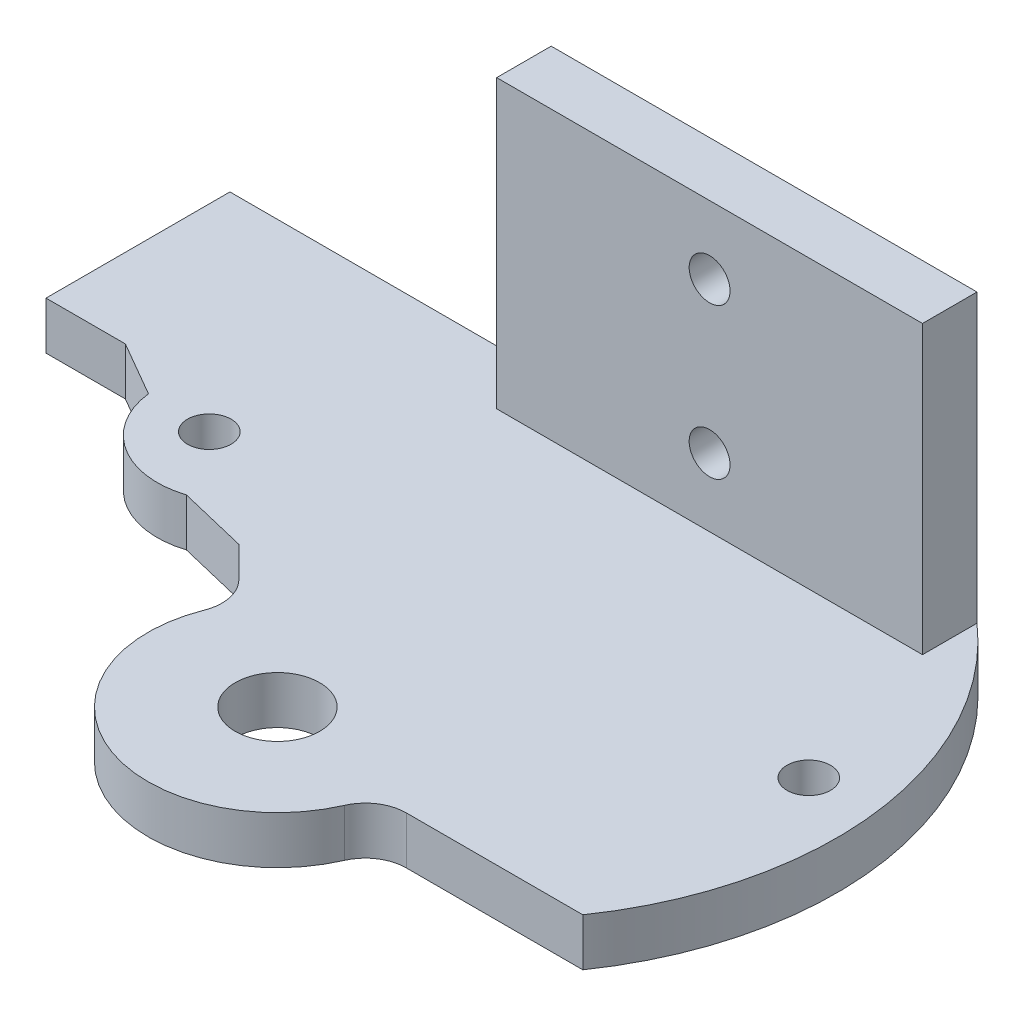
SolidWorks part; units mm, degrees
ref_plane "Alzado" through (0, 0, 0) normal (0, 0, 1) x (1, 0, 0)
ref_plane "Planta" through (0, 0, 0) normal (0, 1, 0) x (1, 0, 0)
ref_plane "Vista lateral" through (0, 0, 0) normal (1, 0, 0) x (0, 0, -1)
sketch "Croquis1" plane through (0, 0, 0) normal (0, 1, 0) x (1, 0, 0)
  line L0 (-35, 32.5) -> (35, -32.5) construction
  line L1 (-35, 32.5) -> (35, 32.5)
  line L2 (-35, 32.5) -> (-35, -32.5)
  line L3 (-35, -32.5) -> (35, -32.5)
  line L4 (35, 32.5) -> (35, -32.5)
  dimension "D1" = 70
  dimension "D2" = 65
extrude "Extruir1" add sketch "Croquis1" along normal blind 3.5
sketch "Croquis2" plane through (0, 3.5, 0) normal (0, 1, 0) x (1, 0, 0)
  line L0 (0, 32.5) -> (0, -32.5) construction
  line L1 (35, 32.5) -> (-35, 32.5) construction
  line L2 (-35, -32.5) -> (35, -32.5) construction
  circle A0 centre (0, -17.5) radius 3.1
  dimension "D1" = 6.2
  dimension "D2" = 15
extrude "Extruir2" cut sketch "Croquis2" against normal blind 5
sketch "Croquis3" plane through (0, 3.5, 0) normal (0, 1, 0) x (1, 0, 0)
  line L0 (0, -32.5) -> (0, 32.5) construction
  line L1 (-35, -32.5) -> (35, -32.5) construction
  line L2 (35, 32.5) -> (-35, 32.5) construction
  line L3 (-32.9868, -32.5) -> (-32.9868, 32.5) construction
  line L4 (-32.9868, 1.5) -> (-12.9615, 1.5)
  line L5 (18.8496, -32.5) -> (18.8496, 32.5) construction
  line L6 (-32.9868, 3.5) -> (18.8496, 3.5) construction
  line L7 (-32.9868, 2) -> (0, 2) construction
  line L8 (-32.9868, 11.5) -> (18.8496, 11.5) construction
  line L9 (0, -17.5) -> (-14.8492, -2.6508) construction
  line L10 (0, -17.5) -> (14.8492, -2.6508) construction
  line L11 (0, 2) -> (18.8496, 2) construction
  line L12 (-32.9868, 2) -> (18.8496, 2) construction
  line L13 (-32.9868, 12) -> (18.8496, 12)
  line L14 (-5.3033, -12.1967) -> (-16.2635, -1.2365) construction
  line L15 (12.9615, 1.5) -> (18.8496, 1.5)
  line L16 (-32.9868, 1.5) -> (18.8496, 1.5) construction
  line L17 (7.9844, -18) -> (22.9946, -18)
  line L18 (-5.9993, -12.2078) -> (-16.6132, -1.5939)
  line L19 (0, -17.5) -> (23, -17.5) construction
  line L20 (7.5, -17.5) -> (23, -17.5) construction
  line L21 (-5.6569, -12.5503) -> (-16.617, -1.5901) construction
  line L22 (7.5, -18) -> (23, -18) construction
  line L23 (-32.9868, 12) -> (-32.9868, 1.5)
  line L24 (18.8496, 12) -> (18.8496, 1.5)
  line L25 (-34.4868, 13.5) -> (20.3496, 13.5)
  line L26 (20.3496, 13.5) -> (20.3496, 0)
  line L27 (17.1464, 0) -> (20.3496, 0)
  line L28 (9.2871, -19.5) -> (24.4182, -19.5)
  line L29 (-7.9812, -12.3473) -> (-18.6805, -1.6479)
  line L30 (-34.4868, 0) -> (-17.1464, 0)
  line L31 (-34.4868, 13.5) -> (-34.4868, 0)
  circle A0 centre (0, -17.5) radius 21 construction
  circle A1 centre (0, -17.5) radius 7.5 construction
  arc A2 (-12.9615, 1.5) -> (-16.6132, -1.5939) centre (0, -17.5) ccw
  circle A3 centre (0, -17.5) radius 23 construction
  arc A4 (-5.9993, -12.2078) -> (7.9844, -18) centre (0, -17.5) ccw
  arc A5 (22.9946, -18) -> (12.9615, 1.5) centre (0, -17.5) ccw
  arc A6 (24.4182, -19.5) -> (17.1464, 0) centre (0, -17.5) ccw
  arc A7 (-7.9812, -12.3473) -> (9.2871, -19.5) centre (0, -17.5) ccw
  arc A8 (-17.1464, 0) -> (-18.6805, -1.6479) centre (0, -17.5) ccw
  dimension "D3" = 42
  dimension "D8" = 15
  dimension "D9" = 46
  dimension "D14" = 0.5
  dimension "D2" = 51.8364
  dimension "D6" = 90
  dimension "D7" = 45
  dimension "D1" = 32.9868
  dimension "D4" = 1.5
  dimension "D5" = 9.5
  dimension "D10" = 2
  dimension "D11" = 0.5
  dimension "D12" = 0.5
  dimension "D13" = 0.5
  dimension "D15" = 1.5
extrude "Extruir3" add sketch "Croquis3" along normal blind 10
sketch "Croquis4" plane through (0, 3.5, 0) normal (0, 1, 0) x (1, 0, 0)
  line L0 (-34.4868, 0) -> (-17.1464, 0) construction
  line L1 (-34.4868, 13.5) -> (-34.4868, 0) construction
  line L2 (20.3496, 13.5) -> (-34.4868, 13.5) construction
  line L3 (20.3496, 0) -> (20.3496, 13.5) construction
  line L4 (17.1464, 0) -> (20.3496, 0) construction
  line L5 (9.2871, -19.5) -> (24.4182, -19.5) construction
  line L6 (-18.6805, -1.6479) -> (-7.9812, -12.3473) construction
  line L7 (-34.4868, 0) -> (-17.1464, 0)
  line L8 (-34.4868, 13.5) -> (-34.4868, 0)
  line L9 (20.3496, 13.5) -> (-34.4868, 13.5)
  line L10 (20.3496, 0) -> (20.3496, 13.5)
  line L11 (17.1464, 0) -> (20.3496, 0)
  line L12 (9.2871, -19.5) -> (24.4182, -19.5)
  line L13 (-18.6805, -1.6479) -> (-7.9812, -12.3473)
  arc A0 (-17.1464, 0) -> (-18.6805, -1.6479) centre (0, -17.5) ccw construction
  arc A1 (24.4182, -19.5) -> (17.1464, 0) centre (0, -17.5) ccw construction
  arc A2 (-7.9812, -12.3473) -> (9.2871, -19.5) centre (0, -17.5) ccw construction
  arc A3 (-17.1464, 0) -> (-18.6805, -1.6479) centre (0, -17.5) ccw
  arc A4 (24.4182, -19.5) -> (17.1464, 0) centre (0, -17.5) ccw
  arc A5 (-7.9812, -12.3473) -> (9.2871, -19.5) centre (0, -17.5) ccw
extrude "Extruir4" cut sketch "Croquis4" against normal blind 10 flip side to cut
fillet "Redondeo1" radius 3 4 edges at (9.2871, 6.75, 19.5) (-7.9812, 6.75, 12.3473) (7.9844, 8.5, 18) (-5.9993, 8.5, 12.2078)
sketch "Croquis5" plane through (0, 0, 0) normal (0, -1, 0) x (1, 0, 0)
  line L0 (-18.6805, 1.6479) -> (-9.5151, 10.8133) construction
  line L1 (-34.4868, 0) -> (-17.1464, 0) construction
  line L2 (-18.6805, 1.6479) -> (-14.4379, 5.8906)
  line L3 (-24.4498, 0) -> (-17.1464, 0)
  line L4 (20.3496, 0) -> (20.3496, -13.5) construction
  line L5 (17.1464, 0) -> (20.3496, 0) construction
  line L6 (20.3496, 0) -> (20.3496, -13.5)
  line L7 (17.1464, 0) -> (20.3496, 0)
  arc A0 (-14.4379, 5.8906) -> (-24.4498, 0) centre (-18.6805, 1.6479) ccw
  arc A1 (-18.6805, 1.6479) -> (-17.1464, 0) centre (0, 17.5) ccw construction
  arc A2 (-18.6805, 1.6479) -> (-17.1464, 0) centre (0, 17.5) ccw
  arc A3 (24.4182, 19.5) -> (20.3496, -13.5) centre (3.8531, 5.2847) cw
  arc A4 (17.1464, 0) -> (24.4182, 19.5) centre (0, 17.5) ccw construction
  arc A5 (17.1464, 0) -> (24.4182, 19.5) centre (0, 17.5) ccw
  dimension "D1" = 12
  dimension "D2" = 25
extrude "Extruir5" add sketch "Croquis5" against normal up to surface (13.5 mm away) up to face at (-1.8278, 13.5, 5.5887)
chamfer "Chaflán1" distance 5 angle 45 2 edges at (-14.4379, 6.75, 5.8906) (-24.4498, 6.75, 0) first distance on face at (-20.5835, 6.75, 4.8823) first distance on face at (-29.4683, 6.75, 0)
sketch "Croquis6" plane through (0, 13.5, 0) normal (0, 1, 0) x (1, 0, 0)
  line L7 (-34.4868, 13.5) -> (-34.4868, 0)
  line L8 (-34.4868, 0) -> (-28.6614, 0)
  line L9 (-28.6614, 0) -> (-24.6424, -2.3231)
  line L10 (-16.83, -7.3554) -> (-11.7523, -8.5761)
  line L11 (-11.7523, -8.5761) -> (-9.5151, -10.8133)
  line L12 (11.4564, -19.5) -> (24.4182, -19.5)
  line L13 (20.3496, 13.5) -> (-34.4868, 13.5)
  line L14 (-34.4868, 13.5) -> (-34.4868, 0)
  line L15 (-34.4868, 0) -> (-28.6614, 0)
  line L16 (-28.6614, 0) -> (-24.6424, -2.3231)
  line L17 (-16.83, -7.3554) -> (-11.7523, -8.5761)
  line L18 (-11.7523, -8.5761) -> (-9.5151, -10.8133)
  line L19 (11.4564, -19.5) -> (24.4182, -19.5)
  line L20 (20.3496, 13.5) -> (-34.4868, 13.5)
  arc A5 (-24.6424, -2.3231) -> (-16.83, -7.3554) centre (-18.6805, -1.6479) ccw
  arc A6 (-8.8437, -14.0303) -> (-9.5151, -10.8133) centre (-11.6365, -12.9346) ccw
  arc A7 (-8.8437, -14.0303) -> (8.7069, -21.3) centre (0, -17.5) ccw
  arc A8 (11.4564, -19.5) -> (8.7069, -21.3) centre (11.4564, -22.5) ccw
  arc A9 (24.4182, -19.5) -> (20.3496, 13.5) centre (3.8531, -5.2847) ccw
  arc A10 (-24.6424, -2.3231) -> (-16.83, -7.3554) centre (-18.6805, -1.6479) ccw
  arc A11 (-8.8437, -14.0303) -> (-9.5151, -10.8133) centre (-11.6365, -12.9346) ccw
  arc A12 (-8.8437, -14.0303) -> (8.7069, -21.3) centre (0, -17.5) ccw
  arc A13 (11.4564, -19.5) -> (8.7069, -21.3) centre (11.4564, -22.5) ccw
  arc A14 (24.4182, -19.5) -> (20.3496, 13.5) centre (3.8531, -5.2847) ccw
  dimension "D1" = 0
extrude "Extruir6" add sketch "Croquis6" along normal blind 3.5 separate body
sketch "Croquis7" plane through (0, 17, 0) normal (0, 1, 0) x (1, 0, 0)
  line L0 (20.3496, 13.5) -> (-34.4868, 13.5) construction
  circle A0 centre (-20, -2.5) radius 1.6
  circle A1 centre (24, -2.5) radius 1.6
  dimension "D1" = 3.2
  dimension "D2" = 16
  dimension "D3" = 20
  dimension "D4" = 24
extrude "Extruir7" cut sketch "Croquis7" against normal through all
sketch "Croquis8" plane through (0, 17, 0) normal (0, 1, 0) x (1, 0, 0)
  circle A0 centre (0, -17.5) radius 3.1 construction
  circle A1 centre (0, -17.5) radius 3.1
extrude "Extruir8" cut sketch "Croquis8" against normal blind 5
sketch "Croquis9" plane through (0, 13.5, 0) normal (0, 1, 0) x (1, 0, 0)
  line L0 (18.8496, 1.5) -> (18.8496, 12) construction
  line L1 (18.8496, 1.5) -> (18.8496, 12)
  line L2 (19.5496, 1.5) -> (19.5496, 12)
  line L3 (18.8496, 12) -> (19.5496, 12)
  line L4 (18.8496, 1.5) -> (19.5496, 1.5)
  dimension "D1" = 0.7
extrude "Extruir9" cut sketch "Croquis9" against normal up to surface (10 mm away) up to face at (-1.6185, 3.5, 4.8365)
sketch "Croquis10" plane through (19.5496, 0, 0) normal (-1, 0, 0) x (0, 0, 1)
  line L0 (-5.875, 13.5) -> (-5.875, 3.5) construction
  line L3 (-1.5, 13.5) -> (-12, 13.5) construction
  line L4 (-12, 3.5) -> (-12, 13.5) construction
  line L5 (-5.875, 13.5) -> (-12, 3.5) construction
  line L6 (-12, 3.5) -> (-1.5, 3.5) construction
  line L7 (-8.9375, 8.5) -> (-12, 13.5) construction
  line L8 (19.5, 13.5) -> (-13.5, 13.5) construction
  line L10 (-7.4062, 11) -> (-10.4687, 11)
  line L11 (-7.4062, 11) -> (-7.4062, 6)
  line L12 (-7.4062, 6) -> (-10.4687, 6)
  line L13 (-10.4687, 11) -> (-10.4687, 6)
  dimension "D1" = 6.125
  dimension "D2" = 5
  dimension "D3" = 3.0625
extrude "Extruir10" cut sketch "Croquis10" against normal blind 10 and the other way through all
delete or keep bodies "Sólido-Eliminar1" type delete bodies bodies 111
sketch "Croquis11" plane through (0, 0, -13.5) normal (0, 0, -1) x (-1, 0, 0)
  line L0 (34.4868, 17) -> (34.4868, 38.056)
  line L2 (-20.3496, 38.056) -> (-20.3496, 17)
  line L3 (-20.3496, 17) -> (34.4868, 17)
  line L4 (34.4868, 38.056) -> (-20.3496, 38.056)
  dimension "D2" = 21.056
extrude "Saliente-Extruir1" add sketch "Croquis11" against normal blind 4
sketch "Croquis15" plane through (0, 0, -9.5) normal (0, 0, 1) x (1, 0, 0)
  line L1 (-34.4868, 38.056) -> (-10.9056, 38.056)
  line L2 (-34.4868, 38.056) -> (-34.4868, 17)
  line L3 (-34.4868, 17) -> (-10.9056, 17)
  line L4 (-10.9056, 38.056) -> (-10.9056, 17)
extrude "Cortar-Extruir3" cut sketch "Croquis15" against normal blind 10
sketch "Croquis16" plane through (0, 0, -9.5) normal (0, 0, 1) x (1, 0, 0)
  line L0 (4.722, 17) -> (4.722, 38.056) construction
  line L1 (20.3496, 17) -> (-10.9056, 17) construction
  line L2 (-10.9056, 38.056) -> (20.3496, 38.056) construction
  circle A0 centre (4.722, 33.056) radius 1.5
  circle A1 centre (4.722, 22) radius 1.5
  dimension "D1" = 3
  dimension "D2" = 3
  dimension "D3" = 5
  dimension "D4" = 5
extrude "Cortar-Extruir4" cut sketch "Croquis16" against normal blind 10
